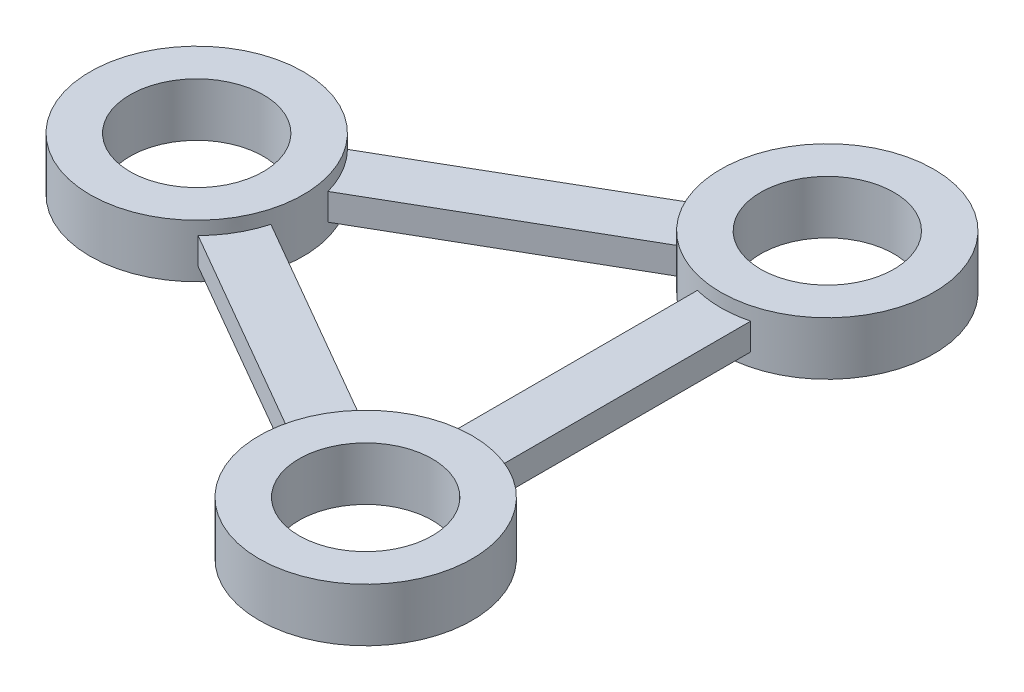
SolidWorks part; units mm, degrees
ref_plane "Ön Düzlem" through (0, 0, 0) normal (0, 0, 1) x (1, 0, 0)
ref_plane "Üst Düzlem" through (0, 0, 0) normal (0, 1, 0) x (1, 0, 0)
ref_plane "Sağ Düzlem" through (0, 0, 0) normal (1, 0, 0) x (0, 0, -1)
sketch "Çizim1" plane through (0, 0, 0) normal (0, 1, 0) x (1, 0, 0)
  line L0 (0, 199.2004) -> (0, -199.2004) construction
  line L1 (-341.3764, 0) -> (168.7617, 0) construction
  line L2 (-10, 47.8702) -> (-10, -47.8702)
  line L3 (10, 47.8702) -> (10, -47.8702)
  line L4 (-121.4553, -28.0267) -> (-38.5412, -75.8958)
  line L5 (-111.4555, -10.7061) -> (-28.5414, -58.5752)
  line L6 (-121.4553, 28.0267) -> (-38.5412, 75.8958)
  line L7 (-111.4555, 10.7061) -> (-28.5414, 58.5752)
  circle A0 centre (0, 86.6) radius 25
  circle A1 centre (0, 86.6) radius 40
  circle A2 centre (0, -86.6) radius 40
  circle A3 centre (0, -86.6) radius 25
  circle A4 centre (-150, 0) radius 25
  circle A5 centre (-150, 0) radius 40.0037
  point P18 (0, 0)
  point P27 (0, 0)
  point P28 (0, 0)
  point P29 (0, 0)
  dimension "D2" = 50
  dimension "D3" = 80
  dimension "D1" = 86.6
  dimension "D4" = 150
  dimension "D5" = 10
  dimension "D6" = 2
  dimension "D7" = 2
extrude "Yükseklik-Ekstrüzyon4" add sketch "Çizim1" along normal blind 10 and the other way blind 10 contours A5 A4 | A2 A3 | A1 A0 region at (-19.4345, 0, -52.9389) region at (0, 0, 47.7314) region at (-111.4839, 0, -5.2497)
extrude "Yükseklik-Ekstrüzyon5" add sketch "Çizim1<6>" along normal blind 5 and the other way blind 5 contours A5 L4 A2 L5 | A5 L7 A1 L6 | L2 A2 L3 A1 region at (0, 0, 0) region at (-74.9984, 0, -43.3009) region at (-74.9984, 0, 43.3009)
sketch "Çizim1<6>" plane through (0, 0, 0) normal (0, 1, 0) x (1, 0, 0) same geometry as "Çizim1"
